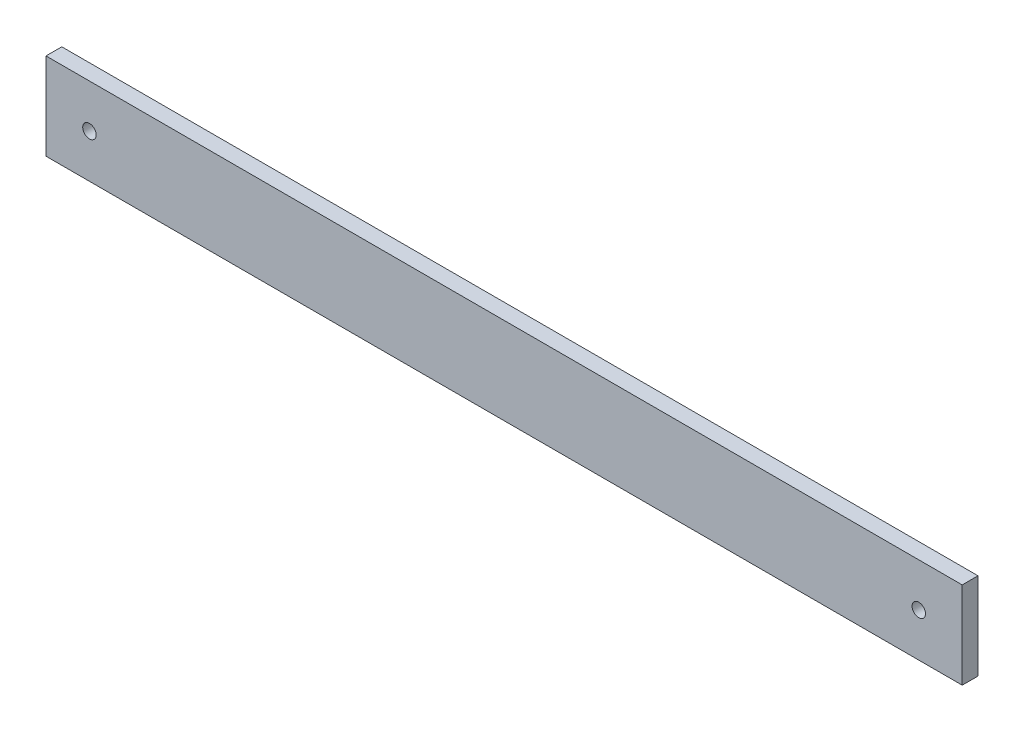
SolidWorks part; units mm, degrees
ref_plane "前视基准面" through (0, 0, 0) normal (0, 0, 1) x (1, 0, 0)
ref_plane "上视基准面" through (0, 0, 0) normal (0, 1, 0) x (1, 0, 0)
ref_plane "右视基准面" through (0, 0, 0) normal (1, 0, 0) x (0, 0, -1)
other "Configuration Table"
sketch "草图1" plane through (0, 0, 0) normal (0, 0, 1) x (1, 0, 0)
  line L1 (-11, -11) -> (221, -11)
  line L2 (-11, -11) -> (-11, 11)
  line L3 (-11, 11) -> (221, 11)
  line L4 (221, -11) -> (221, 11)
  line L5 (-11, -11) -> (221, 11) construction
  line L6 (-11, 11) -> (221, -11) construction
  circle A0 centre (0, 0) radius 1.7
  circle A1 centre (210, 0) radius 1.7
extrude "凸台-拉伸1" add sketch "草图1" along normal mid plane 4
